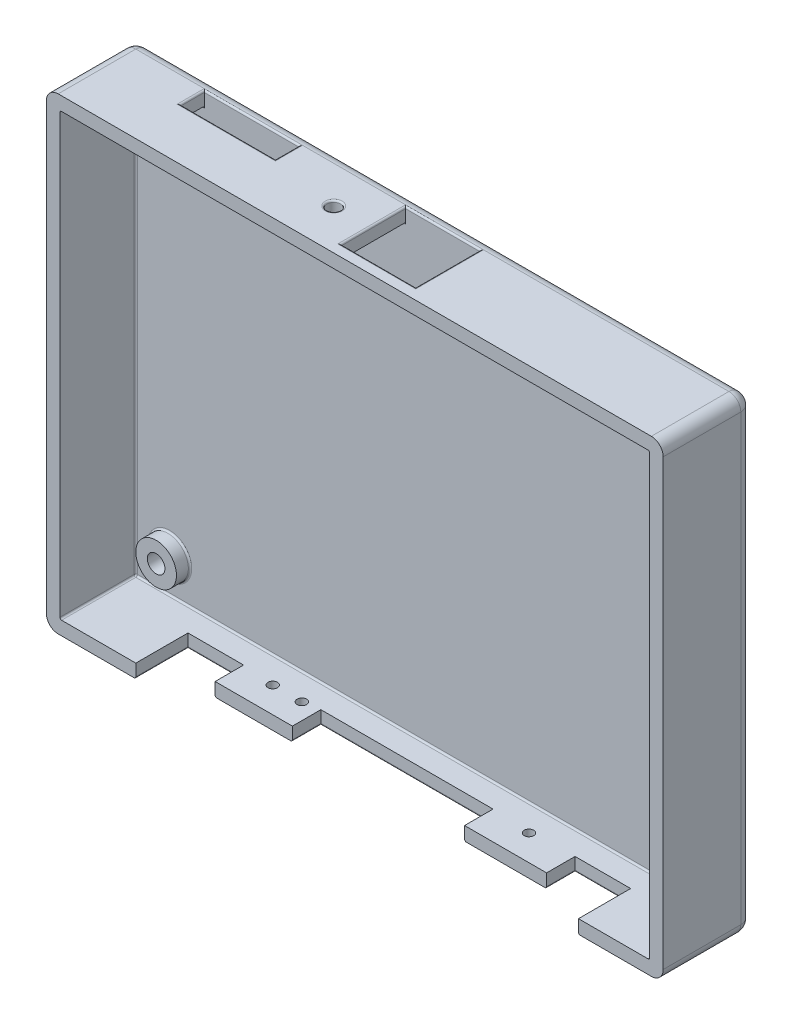
SolidWorks part; units mm, degrees
ref_plane "Front Plane" through (0, 0, 0) normal (0, 0, 1) x (1, 0, 0)
ref_plane "Top Plane" through (0, 0, 0) normal (0, 1, 0) x (1, 0, 0)
ref_plane "Right Plane" through (0, 0, 0) normal (1, 0, 0) x (0, 0, -1)
sketch "Sketch1" plane through (0, 0, 0) normal (0, 0, 1) x (1, 0, 0)
  line L1 (0, 0) -> (91, 0)
  line L2 (0, 0) -> (0, 69)
  line L3 (0, 69) -> (91, 69)
  line L4 (91, 0) -> (91, 69)
extrude "Boss-Extrude1" add sketch "Sketch1" along normal blind 13.2
shell "Shell2" thickness 2 removed face at (45.5, 34.5, 13.2)
sketch "Sketch2" plane through (0, 0, 2) normal (0, 0, 1) x (1, 0, 0)
  line L1 (2, 67) -> (7, 67)
  line L2 (2, 67) -> (2, 62)
  line L3 (2, 62) -> (7, 62)
  line L4 (7, 67) -> (7, 62)
  line L5 (89, 67) -> (84, 67)
  line L6 (89, 67) -> (89, 62)
  line L7 (89, 62) -> (84, 62)
  line L8 (84, 67) -> (84, 62)
  line L9 (89, 2) -> (84, 2)
  line L10 (89, 2) -> (89, 7)
  line L11 (89, 7) -> (84, 7)
  line L12 (84, 2) -> (84, 7)
  line L13 (2, 2) -> (7, 2)
  line L14 (2, 2) -> (2, 7)
  line L15 (2, 7) -> (7, 7)
  line L16 (7, 2) -> (7, 7)
  circle A0 centre (7, 62) radius 3
  circle A1 centre (84, 62) radius 3
  circle A2 centre (84, 7) radius 3
  circle A3 centre (7, 7) radius 3
extrude "Boss-Extrude2" add sketch "Sketch2" along normal blind 2 contours L16 A3 L15 | L15 A3 L16 | L3 A0 L4 | L4 A0 L3 | L8 A1 L7 | L7 A1 L8 | L11 A2 L12 | L12 A2 L11 region at (7.4244, 61.5756, 2) region at (5.7268, 63.2732, 2) region at (85.2732, 63.2732, 2) region at (83.5756, 61.5756, 2) region at (83.5756, 7.4244, 2) region at (85.2732, 5.7268, 2) region at (5.7268, 5.7268, 2) region at (7.4244, 7.4244, 2)
sketch "Sketch3" plane through (0, 0, 4) normal (0, 0, 1) x (1, 0, 0)
  circle A0 centre (7, 62) radius 1.3
  circle A1 centre (84, 62) radius 1.3
  circle A2 centre (84, 7) radius 1.3
  circle A3 centre (7, 7) radius 1.3
extrude "Cut-Extrude1" cut sketch "Sketch3" against normal blind 4
sketch "Sketch5" plane through (0, 0, 0) normal (0, 0, -1) x (-1, 0, 0)
  circle A0 centre (-84, 62) radius 2.1
  circle A1 centre (-7, 62) radius 2.1
  circle A2 centre (-7, 7) radius 2.1
  circle A3 centre (-84, 7) radius 2.1
extrude "Cut-Extrude2" cut sketch "Sketch5" against normal blind 1.7
sketch "Sketch6" plane through (0, 0, 0) normal (0, -1, 0) x (-1, 0, 0)
  line L1 (-13.2, -5.5) -> (-21.4, -5.5)
  line L2 (-13.2, -5.5) -> (-13.2, -13.2)
  line L3 (-13.2, -13.2) -> (-21.4, -13.2)
  line L4 (-21.4, -5.5) -> (-21.4, -13.2)
  line L5 (-70.3, -5.5) -> (-78.5, -5.5)
  line L6 (-70.3, -5.5) -> (-70.3, -13.2)
  line L7 (-70.3, -13.2) -> (-78.5, -13.2)
  line L8 (-78.5, -5.5) -> (-78.5, -13.2)
  line L9 (-32.8, -5.5) -> (-58.2, -5.5)
  line L10 (-32.8, -5.5) -> (-32.8, -13.2)
  line L11 (-32.8, -13.2) -> (-58.2, -13.2)
  line L12 (-58.2, -5.5) -> (-58.2, -13.2)
extrude "Cut-Extrude3" cut sketch "Sketch6" against normal blind 2
sketch "Sketch7" plane through (0, 0, 0) normal (0, -1, 0) x (-1, 0, 0)
  circle A0 centre (-26.1, -5.9) radius 0.7
  circle A1 centre (-30.4, -5.9) radius 0.7
  circle A2 centre (-63.9, -5.9) radius 0.7
extrude "Cut-Extrude4" cut sketch "Sketch7" against normal blind 2
sketch "Sketch8" plane through (0, 69, 0) normal (0, 1, 0) x (1, 0, 0)
  line L1 (12.1, -2) -> (26.1, -2)
  line L2 (12.1, -2) -> (12.1, -5.5)
  line L3 (12.1, -5.5) -> (26.1, -5.5)
  line L4 (26.1, -2) -> (26.1, -5.5)
  line L5 (41.8, -2) -> (52.8, -2)
  line L6 (41.8, -2) -> (41.8, -11.5)
  line L7 (41.8, -11.5) -> (52.8, -11.5)
  line L8 (52.8, -2) -> (52.8, -11.5)
extrude "Cut-Extrude5" cut sketch "Sketch8" against normal blind 2
sketch "Sketch9" plane through (0, 69, 0) normal (0, 1, 0) x (1, 0, 0)
  circle A0 centre (36.4, -7.2) radius 1
extrude "Cut-Extrude6" cut sketch "Sketch9" against normal blind 2
sketch "Sketch10" plane through (0, 0, 0) normal (0, -1, 0) x (-1, 0, 0)
  line L0 (-32.8, -13.2) -> (-32.8, -5.5) construction
  line L1 (-21.4, -13.2) -> (-32.8, -13.2)
  line L2 (-21.4, -13.2) -> (-21.4, -9.7)
  line L3 (-21.4, -9.7) -> (-32.8, -9.7)
  line L4 (-32.8, -13.2) -> (-32.8, -9.7)
  line L5 (-70.3, -13.2) -> (-70.3, -5.5) construction
  line L6 (-58.2, -13.2) -> (-70.3, -13.2)
  line L7 (-58.2, -13.2) -> (-58.2, -9.7)
  line L8 (-58.2, -9.7) -> (-70.3, -9.7)
  line L9 (-70.3, -13.2) -> (-70.3, -9.7)
  point P14 (0, 0)
  point P15 (0, 0)
extrude "Cut-Extrude8" cut sketch "Sketch10" against normal blind 2
fillet "Fillet1" radius 1.75 8 edges at (91, 69, 6.6) (91, 0, 6.6) (0, 0, 6.6) (0, 69, 6.6) (0, 34.5, 0) (45.5, 0, 0) (91, 34.5, 0) (45.5, 69, 0)
fillet "Fillet2" radius 0.25 25 edges at (81.9, 62, 0) (81.9, 7, 0) (4.9, 7, 0) (4.9, 62, 0) (78.5, 0, 9.35) (74.4, 0, 5.5) (70.3, 0, 7.6) (32.8, 0, 7.6) (45.5, 0, 5.5) (58.2, 0, 7.6) (63.9, 0, 5.2) (26.1, 0, 5.2) (30.4, 0, 5.2) (21.4, 0, 7.6) (17.3, 0, 5.5) (13.2, 0, 9.35) (47.3, 69, 11.5) (41.8, 69, 6.75) (52.8, 69, 6.75) (47.3, 69, 2) (36.4, 69, 8.2) (26.1, 69, 3.75) (19.1, 69, 2) (12.1, 69, 3.75) (19.1, 69, 5.5)
fillet "Fillet3" radius 0.25 10 edges at (4, 7, 2) (81, 7, 2) (45.5, 2, 2) (89, 34.5, 2) (70.9, 67, 2) (33.95, 67, 2) (7.05, 67, 2) (2, 34.5, 2) (4, 62, 2) (81, 62, 2)
fillet "Fillet4" radius 0.25 8 edges at (88.9268, 66.9268, 2.0732) (2.0732, 66.9268, 2.0732) (2.0732, 2.0732, 2.0732) (88.9268, 2.0732, 2.0732) (89, 67, 7.725) (2, 67, 7.725) (2, 2, 7.725) (89, 2, 7.725)
sketch "Sketch12" plane through (0, 0, 0) normal (0, 0, -1) x (-1, 0, 0)
  line L1 (-28.5, 20.5) -> (-62.5, 20.5)
  line L2 (-28.5, 20.5) -> (-28.5, 48.5)
  line L3 (-28.5, 48.5) -> (-62.5, 48.5)
  line L4 (-62.5, 20.5) -> (-62.5, 48.5)
extrude "Cut-Extrude9" cut sketch "Sketch12" against normal blind 0.2
fillet "Fillet5" radius 0.2 4 edges at (45.5, 48.5, 0) (62.5, 34.5, 0) (28.5, 34.5, 0) (45.5, 20.5, 0)
